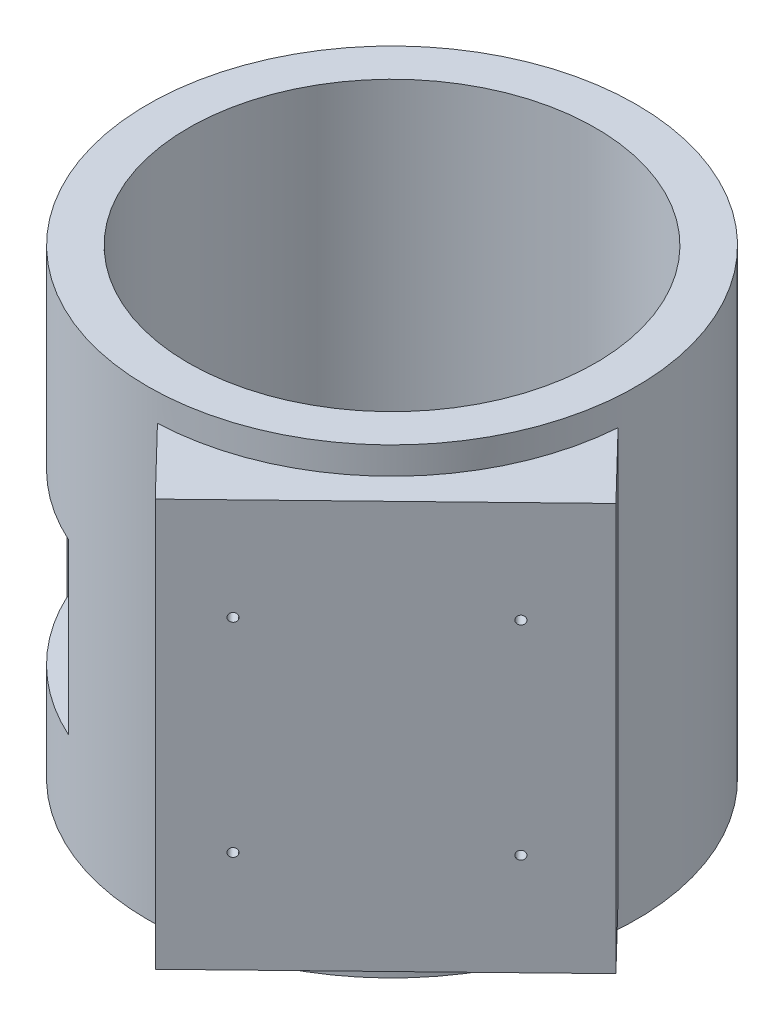
SolidWorks part; units mm, degrees
ref_plane "前视基准面" through (0, 0, 0) normal (0, 0, 1) x (1, 0, 0)
ref_plane "上视基准面" through (0, 0, 0) normal (0, 1, 0) x (1, 0, 0)
ref_plane "右视基准面" through (0, 0, 0) normal (1, 0, 0) x (0, 0, -1)
sketch "草图2" plane through (0, 0, 0) normal (0, 1, 0) x (1, 0, 0)
  circle A0 centre (0, 0) radius 100
  circle A1 centre (0, 0) radius 120
  dimension "D1" = 200
  dimension "D2" = 240
extrude "凸台-拉伸1" add sketch "草图2" along normal blind 226.75
ref_plane "基准面1" through (86.9388, 0, 89.8701) normal (0.6953, 0, 0.7187) x (0.7187, 0, -0.6953)
sketch "草图3" plane through (1112.773, 1150.452, -902.5046) normal (0.6953, 0, 0.7187) x (0.0779, 0.9941, -0.0754)
  line L0 (-1094.5421, 1301.3101) -> (-1273.4815, 1281.799) construction
  line L1 (-1273.4815, 1281.799) -> (-1267.5198, 1227.1231) construction
  line L2 (-1267.5198, 1227.1231) -> (-1088.5804, 1246.6342) construction
  line L3 (-1088.5804, 1246.6342) -> (-1094.5421, 1301.3101) construction
  line L4 (-1276.7333, 1311.6223) -> (-1097.7939, 1331.1333) construction
  line L5 (-1097.7939, 1331.1333) -> (-1103.7556, 1385.8093) construction
  line L6 (-1103.7556, 1385.8093) -> (-1282.6951, 1366.2982) construction
  line L7 (-1282.6951, 1366.2982) -> (-1276.7333, 1311.6223) construction
  line L8 (-1094.5421, 1301.3101) -> (-1273.4815, 1281.799) construction
  line L9 (-1273.4815, 1281.799) -> (-1267.5198, 1227.1231)
  line L10 (-1267.5198, 1227.1231) -> (-1088.5804, 1246.6342)
  line L11 (-1088.5804, 1246.6342) -> (-1094.5421, 1301.3101)
  line L12 (-1276.7333, 1311.6223) -> (-1097.7939, 1331.1333) construction
  line L13 (-1097.7939, 1331.1333) -> (-1103.7556, 1385.8093)
  line L14 (-1103.7556, 1385.8093) -> (-1282.6951, 1366.2982)
  line L15 (-1282.6951, 1366.2982) -> (-1276.7333, 1311.6223)
  line L16 (-1097.7939, 1331.1333) -> (-1094.5421, 1301.3101)
  line L17 (-1273.4815, 1281.799) -> (-1276.7333, 1311.6223)
  line L18 (-1087.8528, 1332.2173) -> (-1094.8985, 1396.8343)
  line L19 (-1094.8985, 1396.8343) -> (-1293.7201, 1375.1553)
  line L20 (-1293.7201, 1375.1553) -> (-1286.6744, 1310.5383)
  line L21 (-1283.4226, 1280.7151) -> (-1286.6744, 1310.5383)
  line L22 (-1283.4226, 1280.7151) -> (-1276.3769, 1216.0981)
  line L23 (-1276.3769, 1216.0981) -> (-1077.5553, 1237.777)
  line L24 (-1077.5553, 1237.777) -> (-1084.601, 1302.394)
  line L25 (-1087.8528, 1332.2173) -> (-1084.601, 1302.394)
  dimension "D1" = 10
extrude "切除-拉伸1" cut sketch "草图3" against normal blind 100 contours L18 L19 L20 L21 L22 L23 L24 L25
sketch "草图4" plane through (1112.773, 1150.452, -902.5046) normal (0.6953, 0, 0.7187) x (0.0779, 0.9941, -0.0754)
  line L0 (-1293.7201, 1375.1553) -> (-1094.8985, 1396.8343) construction
  line L1 (-1276.3769, 1216.0981) -> (-1293.7201, 1375.1553) construction
  line L2 (-1077.5553, 1237.777) -> (-1276.3769, 1216.0981) construction
  line L3 (-1094.8985, 1396.8343) -> (-1077.5553, 1237.777) construction
  line L4 (-1293.7201, 1375.1553) -> (-1094.8985, 1396.8343)
  line L5 (-1276.3769, 1216.0981) -> (-1293.7201, 1375.1553)
  line L6 (-1077.5553, 1237.777) -> (-1276.3769, 1216.0981)
  line L7 (-1094.8985, 1396.8343) -> (-1077.5553, 1237.777)
  line L12 (-1276.7333, 1311.6223) -> (-1097.7939, 1331.1333)
  line L13 (-1097.7939, 1331.1333) -> (-1103.7556, 1385.8093)
  line L14 (-1103.7556, 1385.8093) -> (-1282.6951, 1366.2982)
  line L15 (-1282.6951, 1366.2982) -> (-1276.7333, 1311.6223)
  line L16 (-1276.7333, 1311.6223) -> (-1097.7939, 1331.1333) construction
  line L17 (-1097.7939, 1331.1333) -> (-1103.7556, 1385.8093)
  line L18 (-1103.7556, 1385.8093) -> (-1282.6951, 1366.2982)
  line L19 (-1282.6951, 1366.2982) -> (-1276.7333, 1311.6223)
  line L20 (-1097.7939, 1331.1333) -> (-1094.5421, 1301.3101)
  line L21 (-1276.7333, 1311.6223) -> (-1273.4815, 1281.799)
  line L24 (-1094.5421, 1301.3101) -> (-1273.4815, 1281.799)
  line L25 (-1273.4815, 1281.799) -> (-1267.5198, 1227.1231)
  line L26 (-1267.5198, 1227.1231) -> (-1088.5804, 1246.6342)
  line L27 (-1088.5804, 1246.6342) -> (-1094.5421, 1301.3101)
  line L28 (-1094.5421, 1301.3101) -> (-1273.4815, 1281.799) construction
  line L29 (-1273.4815, 1281.799) -> (-1267.5198, 1227.1231)
  line L30 (-1267.5198, 1227.1231) -> (-1088.5804, 1246.6342)
  line L31 (-1088.5804, 1246.6342) -> (-1094.5421, 1301.3101)
  dimension "D1" = 0
  dimension "D2" = 0
extrude "凸台-拉伸3" add sketch "草图4" against normal up to surface (185.04 mm away) up to face at (55.6231, 113.4142, 57.4985)
sketch "草图5" plane through (0, 213.4142, 0) normal (0, 1, 0) x (1, 0, 0)
  circle A0 centre (0, 0) radius 100 construction
  circle A1 centre (0, 0) radius 100
extrude "切除-拉伸2" cut sketch "草图5" against normal through all both and the other way through all
sketch "草图6" plane through (86.9388, 0, 89.8701) normal (0.6953, 0, 0.7187) x (0.7187, 0, -0.6953)
  line L4 (-80, 13.4142) -> (80, 13.4142)
  line L5 (80, 13.4142) -> (80, 213.4142)
  line L6 (80, 213.4142) -> (-80, 213.4142)
  line L7 (-80, 213.4142) -> (-80, 13.4142)
  line L8 (-80, 13.4142) -> (80, 13.4142)
  line L9 (80, 13.4142) -> (80, 213.4142)
  line L10 (80, 213.4142) -> (-80, 213.4142)
  line L13 (-80, 213.4142) -> (-80, 13.4142)
  dimension "D1" = 0
extrude "凸台-拉伸4" add sketch "草图6" along normal blind 10
sketch "草图7" plane through (93.8917, 0, 97.0574) normal (0.6953, 0, 0.7187) x (0.7187, 0, -0.6953)
  line L4 (70, 203.4142) -> (-70, 203.4142)
  line L6 (70, 203.4142) -> (-70, 203.4142) construction
  line L12 (70, 23.4142) -> (70, 203.4142)
  line L14 (70, 23.4142) -> (70, 203.4142) construction
  line L19 (-70, 23.4142) -> (70, 23.4142)
  line L23 (-70, 23.4142) -> (70, 23.4142) construction
  line L25 (-70, 203.4142) -> (-70, 23.4142)
  line L27 (-70, 203.4142) -> (-70, 23.4142) construction
  circle A0 centre (47, 163.4142) radius 2.5
  circle A1 centre (-53, 163.4142) radius 2.5
  circle A2 centre (-53, 63.4142) radius 2.5
  circle A3 centre (47, 63.4142) radius 2.5
  dimension "D2" = 5
  dimension "D5" = 5
  dimension "D6" = 5
  dimension "D7" = 5
  dimension "D1" = 0
ref_plane "基准面2" through (0, 0, 0) normal (-0.7187, 0, 0.6953) x (0.6953, 0, 0.7187)
ref_plane "基准面3" through (-86.2477, 0, 83.4346) normal (-0.7187, 0, 0.6953) x (0.6953, 0, 0.7187)
sketch "草图9" plane through (-86.2477, 0, 83.4346) normal (-0.7187, 0, 0.6953) x (0.6953, 0, 0.7187)
  line L9 (2.54, 207.6101) -> (2.54, 62.1309) construction
  line L10 (-120, 0) -> (120, 0) construction
  line L11 (-38.96, 131.41) -> (44.04, 131.41)
  line L12 (-38.96, 131.41) -> (-38.96, 48.41)
  line L13 (-38.96, 48.41) -> (44.04, 48.41)
  line L14 (44.04, 131.41) -> (44.04, 48.41)
  line L15 (-38.96, 131.41) -> (44.04, 48.41) construction
  line L16 (-38.96, 48.41) -> (44.04, 131.41) construction
  point P0 (2.54, 89.91)
  dimension "D1" = 83
  dimension "D2" = 83
  dimension "D3" = 48.41
extrude "切除-拉伸8" cut sketch "草图9" against normal blind 29
hole_wizard "M5 螺纹孔1" positions "3D草图1" profile "草图10" tap size "M5" standard "GB" end condition up to next
sketch3d "3D草图1"
  point P0 (55.799, 163.4142, 133.9077)
  point P3 (127.6721, 163.4142, 64.3789)
  point P6 (127.6721, 63.4142, 64.3789)
  point P9 (55.799, 63.4142, 133.9077)
sketch "草图10" plane through (55.799, 163.4142, 133.9077) normal (0, 1, 0) x (0.7187, 0, -0.6953)
  line L0 (0, 0) -> (0, 10)
  line L1 (0, 10) -> (2.1, 10)
  line L2 (2.1, 10) -> (2.1, 0)
  line L5 (2.1, 0) -> (0, 0)
  line L11 (0, -6.35) -> (0, 107.95) construction
  dimension "通孔螺纹孔钻头直径" = 4.2
  dimension "通孔螺纹孔钻头深度" = 10
